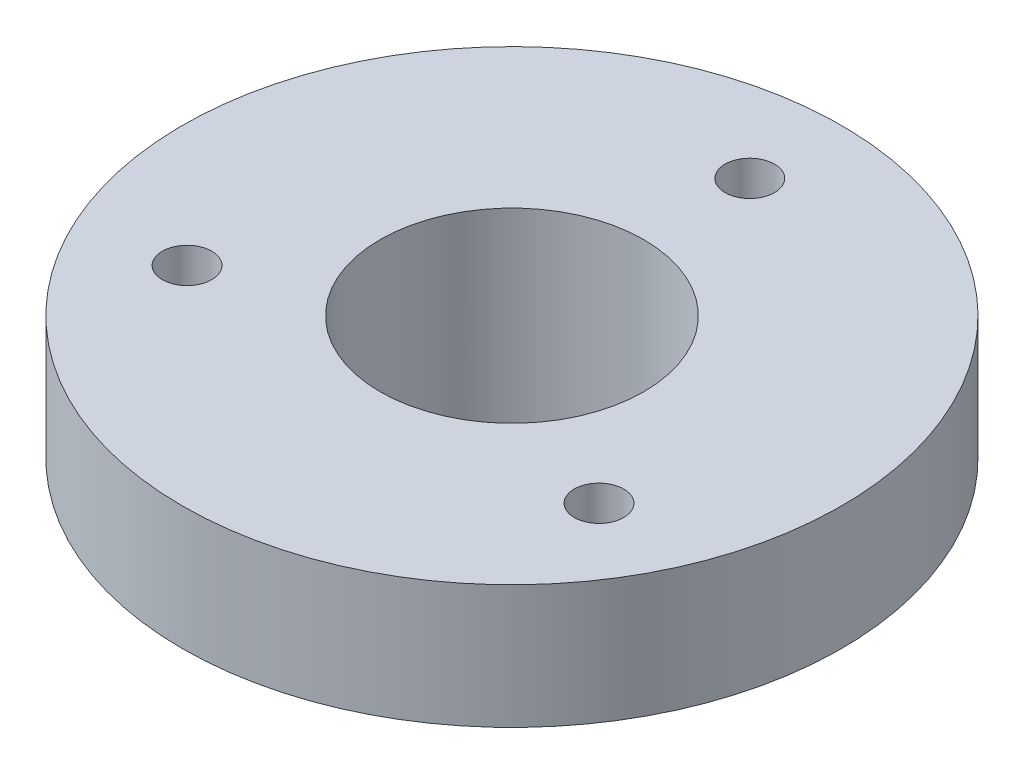
SolidWorks part; units mm, degrees
material "ABS"
ref_plane "Plan de face" through (0, 0, 0) normal (0, 0, 1) x (1, 0, 0)
ref_plane "Plan de dessus" through (0, 0, 0) normal (0, 1, 0) x (1, 0, 0)
ref_plane "Plan de droite" through (0, 0, 0) normal (1, 0, 0) x (0, 0, -1)
sketch "Esquisse1" plane through (0, 0, 0) normal (0, 1, 0) x (1, 0, 0)
  circle A0 centre (0, 0) radius 6.4
  circle A1 centre (0, 0) radius 16
  circle A7 centre (0, 11.547) radius 1.2
  circle A8 centre (10, -5.7735) radius 1.2
  circle A9 centre (-10, -5.7735) radius 1.2
  point P22 (0, 0)
  dimension "D1" = 12.8
  dimension "D2" = 32
  dimension "D3" = 3
  dimension "D5" = 20
  dimension "D6" = 2.4
extrude "Boss.-Extru.1" add sketch "Esquisse1" along normal blind 6
sketch "Esquisse2" plane through (0, 0, 0) normal (0, -1, 0) x (1, 0, 0)
  circle A0 centre (0, 0) radius 8
  circle A1 centre (0, 0) radius 6.4
  circle A3 centre (0, 0) radius 6.4 construction
  dimension "D1" = 16
extrude "Boss.-Extru.2" add sketch "Esquisse2" along normal blind 4
chamfer "Chanfrein1" distance 0.5 angle 45 2 edges at (0, -4, -6.4) (0, 0, 8)
